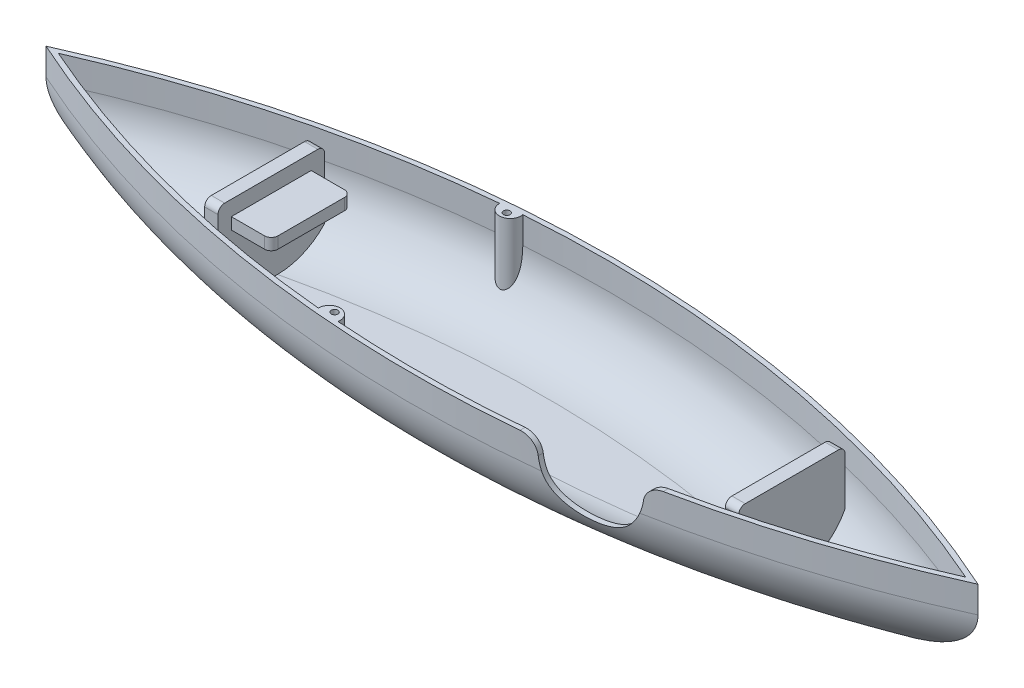
SolidWorks part; units mm, degrees
ref_plane "Front Plane" through (0, 0, 0) normal (0, 0, 1) x (1, 0, 0)
ref_plane "Top Plane" through (0, 0, 0) normal (0, 1, 0) x (1, 0, 0)
ref_plane "Right Plane" through (0, 0, 0) normal (1, 0, 0) x (0, 0, -1)
sketch "Sketch1" plane through (0, 0, 0) normal (0, 1, 0) x (1, 0, 0)
  line L0 (-92, 14) -> (-92, 0) construction
  line L1 (0, 0) -> (-140, 0) construction
  line L2 (0, 0) -> (0, 14)
  line L3 (0, 14) -> (-140, 14) construction
  line L4 (-140, 0) -> (-140, 14)
  line L5 (-140, 7) -> (0, 7) construction
  arc A0 (-140, 7) -> (0, 7) centre (-70, -147.9193) cw
  arc A1 (-140, 7) -> (0, 7) centre (-70, 161.9193) ccw
  dimension "D4" = 170
  dimension "D1" = 14
  dimension "D2" = 140
  dimension "D3" = 48
extrude "Boss-Extrude1" add sketch "Sketch1" along normal blind 14 contours A1 A0
fillet "Fillet1" radius 10 2 edges at (-70, 0, -22.0807) (-70, 0, 8.0807)
shell "Shell1" thickness 0.75 removed face at (-70, 14, -7)
sketch "Sketch2" plane through (0, 14, 0) normal (0, 1, 0) x (1, 0, 0)
  line L0 (0, 7) -> (-140, 7) construction
  arc A4 (-85.4737, 20.6218) -> (-82.2627, 20.8858) centre (-70, -147.9193) cw
  arc A7 (-85.4737, 20.6218) -> (-82.2627, 20.8858) centre (-83.8542, 20.5835) ccw
  circle A10 centre (-83.7252, -5.9279) radius 0.5
  arc A11 (-85.4737, -6.6218) -> (-82.2627, -6.8858) centre (-83.8542, -6.5835) cw
  arc A12 (-138.1584, 7) -> (-1.8416, 7) centre (-70, 161.9193) ccw construction
  arc A13 (-85.4737, -6.6218) -> (-82.2627, -6.8858) centre (-70, 161.9193) ccw
  circle A14 centre (-83.7252, 19.9279) radius 0.5
  dimension "D1" = 1
  dimension "D2" = 1.62
sketch "Sketch3" plane through (0, 14, 0) normal (0, 1, 0) x (1, 0, 0)
  line L0 (-30, 7) -> (-24.7608, 7) construction
  line L1 (-29.9633, 15) -> (-27.9633, 15)
  line L2 (-29.9633, 15) -> (-29.9633, -1)
  line L3 (-29.9633, -1) -> (-27.9633, -1)
  line L4 (-27.9633, 15) -> (-27.9633, -1)
  line L5 (-30.0633, 0.5) -> (-30.0633, 13.5) construction
  spline S0 degree 3 poles (-1.8416, 7) (-1.8484, 7.0001) (-1.8619, 7.0003) (-1.9765, 6.9997) (-2.203, 7.0001) (-2.6335, 6.9999) (-3.5131, 7) (-4.9712, 7) (-7.3642, 7) (-10.6292, 7) (-14.6042, 7) (-18.8422, 7) (-23.1671, 7) (-26.8913, 7) (-29.1867, 7) (-30, 7) knots 0 0 0 0 0.016404 0.033074 0.050246 0.081671 0.116252 0.181085 0.258297 0.374945 0.510238 0.645769 0.781747 0.922668 1 1 1 1 construction
  dimension "D1" = 0.1
  dimension "D2" = 16
  dimension "D3" = 2
extrude "Boss-Extrude3" add sketch "Sketch3" against normal up to next contours L4 L3 L2 L1
sketch "Sketch4" plane through (0, 14, 0) normal (0, 1, 0) x (1, 0, 0)
  line L0 (-110, 7) -> (-106.1633, 7) construction
  line L1 (-106.1633, 15) -> (-108.1633, 15)
  line L2 (-106.1633, 15) -> (-106.1633, -1)
  line L3 (-106.1633, -1) -> (-108.1633, -1)
  line L4 (-108.1633, 15) -> (-108.1633, -1)
  line L5 (-106.0633, 13.5) -> (-106.0633, 0.5) construction
  dimension "D1" = 0.1
  dimension "D2" = 2
  dimension "D3" = 16
extrude "Boss-Extrude4" add sketch "Sketch4" against normal up to next contours L4 L3 L2 L1
sketch "Sketch7" plane through (-68.0633, 14.3388, -7) normal (0, 0, 1) x (1, 0, 0)
  line L0 (-38.1, -10.5165) -> (-38.1, -0.3388) construction
  line L1 (-38.1, -2.6) -> (-32.1, -2.6)
  line L2 (-38.1, -2.6) -> (-38.1, -4.3388)
  line L3 (-38.1, -4.3388) -> (-32.1, -4.3388)
  line L4 (-32.1, -2.6) -> (-32.1, -4.3388)
  line L5 (66.2217, -4.3388) -> (-70.0951, -4.3388) construction
  line L6 (-38, -2.5) -> (38, -2.5) construction
  line L7 (38.1, -9.3629) -> (38.1, -0.3388) construction
  line L8 (38.1, -2.6) -> (37.1, -2.6)
  line L9 (38.1, -2.6) -> (38.1, -4.3388)
  line L10 (38.1, -4.3388) -> (37.1, -4.3388)
  line L11 (37.1, -2.6) -> (37.1, -4.3388)
  dimension "D1" = 0.1
  dimension "D2" = 6
  dimension "D3" = 0.1
  dimension "D4" = 1
extrude "Boss-Extrude5" add sketch "Sketch7" along normal mid plane 12
ref_plane "Plane1" through (0, 0, -7) normal (0, 0, -1) x (-1, 0, 0)
extrude "Boss-Extrude6" add sketch "Sketch2" against normal up to next
sketch "Sketch8" plane through (-68.0633, 14.3388, -7) normal (0, 0, 1) x (1, 0, 0)
  line L0 (68.0633, -0.3388) -> (-71.9367, -0.3388) construction
  line L1 (16.0702, -1.7236) -> (16.0702, -7.2039) construction
  line L2 (16.0702, -1.7236) -> (16.0702, -0.3388)
  line L3 (23, 0) -> (23.0002, -1.7236) construction
  line L4 (29.9302, -1.7236) -> (29.9302, -0.3388)
  line L5 (29.9302, -0.3388) -> (16.0702, -0.3388)
  arc A0 (16.0702, -1.7236) -> (29.9302, -1.7236) centre (23.0002, -1.7236) ccw
  dimension "D1" = 6.93
extrude "Cut-Extrude1" cut sketch "Sketch8" along normal through all
fillet "Fillet2" radius 2.5 2 edges at (-38.1331, 14, 4.6854) (-51.9931, 14, 6.7472)
fillet "Fillet3" radius 1 6 edges at (-100.1633, 10.8694, -13) (-100.1633, 10.8694, -1) (-107.1633, 14, -15) (-107.1633, 14, 1) (-28.9633, 14, -15) (-28.9633, 14, 1)
